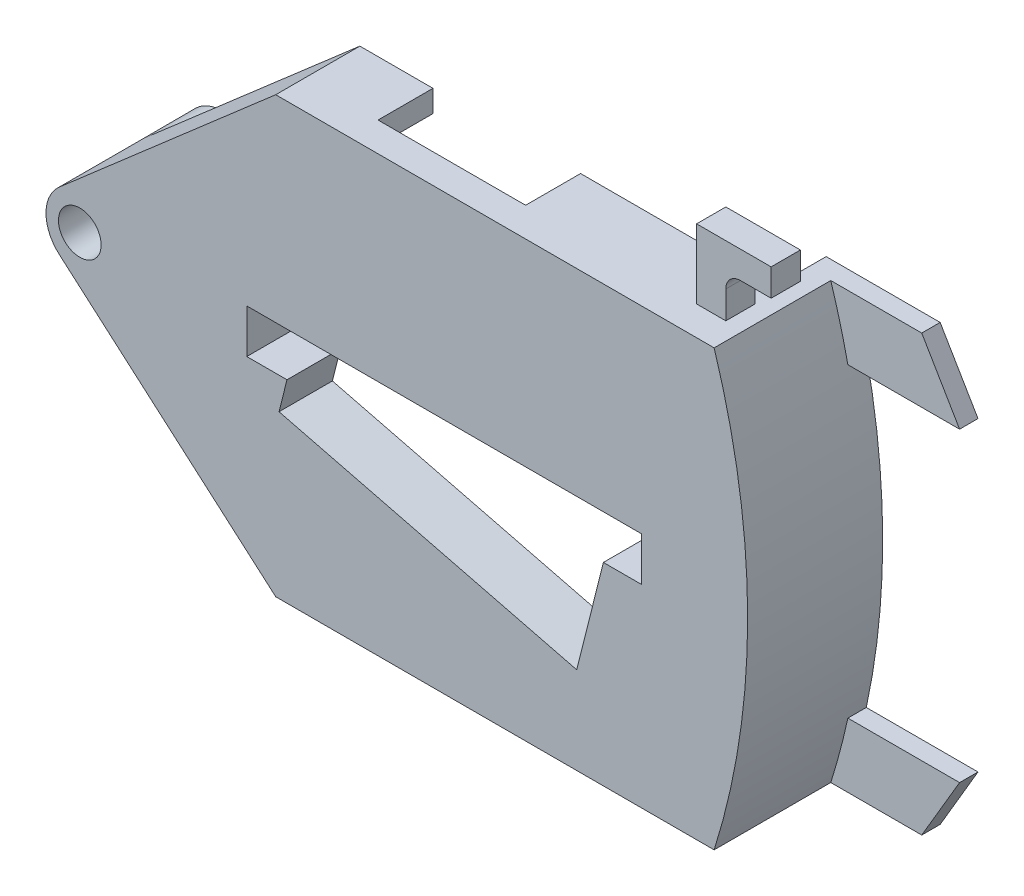
SolidWorks part; units mm, degrees
material "PW50:30:C1:0:1:2:Re:16:Tr:20:"
ref_plane "Plane1" through (0, 0, 0) normal (0, 0, 1) x (1, 0, 0)
ref_plane "Plane2" through (0, 0, 0) normal (0, 1, 0) x (1, 0, 0)
ref_plane "Plane3" through (0, 0, 0) normal (1, 0, 0) x (0, 0, -1)
other "Configuration Table"
sketch "Sketch1" plane through (0, 0, 0) normal (0, 0, 1) x (1, 0, 0)
  line L0 (-12.6668, 0) -> (55.8663, 0) construction
  line L1 (0, 0) -> (17.1073, 14.875)
  line L2 (0, 0) -> (17.1073, -14.875)
  line L3 (17.1073, 14.875) -> (47.1073, 14.875)
  line L4 (17.1073, -14.875) -> (47.1073, -14.875)
  arc A0 (47.1073, -14.875) -> (47.1073, 14.875) centre (0, 0) ccw
  dimension "D2" = 49.4
  dimension "D1" = 29.75
  dimension "D3" = 30
extrude "Base-Extrude" add sketch "Sketch1" along normal blind 5.76
sketch "Sketch2" plane through (0, 0, 5.76) normal (0, 0, 1) x (1, 0, 0)
  line L2 (0, 0) -> (17.1073, 14.875) construction
  line L3 (0, 0) -> (17.1073, -14.875) construction
  circle A0 centre (4.0387, 0) radius 2.65
  dimension "D1" = 5.3
extrude "Boss-Extrude1" add sketch "Sketch2" against normal blind 9.45
sketch "Sketch3" plane through (0, 0, 5.76) normal (0, 0, 1) x (1, 0, 0)
  line L0 (0, 0) -> (17.1073, -14.875) construction
  line L1 (0, 0) -> (17.1073, 14.875) construction
  line L2 (0, 0) -> (2.2999, -1.9998)
  line L3 (0, 0) -> (2.2999, 1.9998)
  arc A0 (2.2999, 1.9998) -> (2.2999, -1.9998) centre (4.0387, 0) ccw construction
  arc A1 (2.2999, 1.9998) -> (2.2999, -1.9998) centre (4.0387, 0) ccw
extrude "Cut-Extrude3" cut sketch "Sketch3" against normal through all
sketch "Sketch4" plane through (0, 0, -3.69) normal (0, 0, -1) x (-1, 0, 0)
  circle A0 centre (-4.0387, 0) radius 1.37
  dimension "D1" = 2.74
extrude "Boss-Extrude2" add sketch "Sketch4" along normal blind 2.64 draft 1 draft outward yes
sketch "Sketch6" plane through (0, 0, 5.76) normal (0, 0, 1) x (1, 0, 0)
  line L0 (1.3887, 0) -> (49.4, 0) construction
  line L1 (1.3887, 0) -> (1.3887, 1.0249) construction
  arc A1 (47.1073, -14.875) -> (47.1073, 14.875) centre (0, 0) ccw construction
  arc A2 (2.2999, 1.9998) -> (2.2999, -1.9998) centre (4.0387, 0) ccw construction
  dimension "D1" = 48.0113
sketch "Sketch7" plane through (0, 0, 5.76) normal (0, 0, 1) x (1, 0, 0)
  circle A2 centre (3.7016, 0) radius 1.15
  dimension "D1" = 2.3
extrude "Cut-Extrude4" cut sketch "Sketch7" against normal offset from surface (11.09 mm away) 1 up to face at (2.6226, 0, -6.33)
sketch "Sketch8" plane through (0, 0, 5.76) normal (0, 0, 1) x (1, 0, 0)
  line L0 (-0.719, 1.37) -> (50.999, 1.37) construction
  line L1 (15.1282, 1.37) -> (42.1282, 1.37)
  line L2 (42.1282, 1.37) -> (42.1282, -1.63)
  line L3 (42.1282, -1.63) -> (39.5282, -1.63)
  line L4 (39.5282, -1.63) -> (37.7042, -8.9048)
  line L5 (37.7042, -8.9048) -> (17.3347, -3.7977)
  line L6 (17.3347, -3.7977) -> (17.8782, -1.63)
  line L7 (17.8782, -1.63) -> (15.1282, -1.63)
  line L8 (15.1282, -1.63) -> (15.1282, 1.37)
  circle A0 centre (4.0387, 0) radius 1.37 construction
  dimension "D1" = 27
  dimension "D2" = 21
  dimension "D3" = 3
  dimension "D4" = 3
  dimension "D5" = 7.5
  dimension "D6" = 2.6
  dimension "D7" = 2.75
  dimension "D8" = 2.2348
extrude "Cut-Extrude5" cut sketch "Sketch8" against normal through all
sketch "Sketch9" plane through (0, 0, 0) normal (0, 0, -1) x (-1, 0, 0)
  line L12 (-3.2841, 0.8678) -> (-17.6682, 13.375)
  line L13 (-17.6682, 13.375) -> (-45.9948, 13.375)
  line L14 (-17.6682, -13.375) -> (-45.9948, -13.375)
  line L15 (-3.2841, -0.8678) -> (-17.6682, -13.375)
  line L16 (-5.0857, 2.4344) -> (-17.6682, 13.375)
  line L17 (-17.6682, 13.375) -> (-45.9948, 13.375)
  line L18 (-17.6682, -13.375) -> (-45.9948, -13.375)
  line L19 (-5.0857, -2.4344) -> (-17.6682, -13.375)
  circle A4 centre (-4.0387, 0) radius 2.65 construction
  arc A5 (-45.9948, 13.375) -> (-45.9948, -13.375) centre (0, 0) ccw
  arc A6 (-45.9948, 13.375) -> (-45.9948, -13.375) centre (0, 0) ccw
  arc A7 (-5.0857, 2.4344) -> (-5.0857, -2.4344) centre (-4.0387, 0) ccw
  dimension "D1" = 1.5
extrude "Cut-Extrude6" cut sketch "Sketch9" against normal offset from surface (3.76 mm away) 2 up to face at (4.8516, 0, 5.76)
sketch "Sketch10" plane through (0, 0, 3.76) normal (0, 0, -1) x (-1, 0, 0)
  line L0 (-15.1282, 1.37) -> (-15.1282, -1.63) construction
  line L1 (-15.1282, -1.63) -> (-17.8782, -1.63) construction
  line L2 (-17.8782, -1.63) -> (-17.3347, -3.7977) construction
  line L3 (-17.3347, -3.7977) -> (-37.7042, -8.9048) construction
  line L4 (-37.7042, -8.9048) -> (-39.5282, -1.63) construction
  line L5 (-39.5282, -1.63) -> (-42.1282, -1.63) construction
  line L6 (-42.1282, -1.63) -> (-42.1282, 1.37) construction
  line L7 (-42.1282, 1.37) -> (-15.1282, 1.37) construction
  line L8 (-43.1282, -2.63) -> (-43.1282, 2.37)
  line L9 (-40.3084, -2.63) -> (-43.1282, -2.63)
  line L10 (-38.431, -10.118) -> (-40.3084, -2.63)
  line L11 (-16.1215, -4.5245) -> (-38.431, -10.118)
  line L12 (-16.5965, -2.63) -> (-16.1215, -4.5245)
  line L13 (-14.1282, -2.63) -> (-16.5965, -2.63)
  line L14 (-14.1282, 2.37) -> (-14.1282, -2.63)
  line L15 (-43.1282, 2.37) -> (-14.1282, 2.37)
  line L16 (-43.1282, -2.63) -> (-43.1282, 2.37)
  line L17 (-40.3084, -2.63) -> (-43.1282, -2.63)
  line L18 (-38.431, -10.118) -> (-40.3084, -2.63)
  line L19 (-16.1215, -4.5245) -> (-38.431, -10.118)
  line L20 (-16.5965, -2.63) -> (-16.1215, -4.5245)
  line L21 (-14.1282, -2.63) -> (-16.5965, -2.63)
  line L22 (-14.1282, 2.37) -> (-14.1282, -2.63)
  line L23 (-43.1282, 2.37) -> (-14.1282, 2.37)
  line L24 (-15.1282, 1.37) -> (-15.1282, -1.63)
  line L25 (-15.1282, -1.63) -> (-17.8782, -1.63)
  line L26 (-17.8782, -1.63) -> (-17.3347, -3.7977)
  line L27 (-17.3347, -3.7977) -> (-37.7042, -8.9048)
  line L28 (-37.7042, -8.9048) -> (-39.5282, -1.63)
  line L29 (-39.5282, -1.63) -> (-42.1282, -1.63)
  line L30 (-42.1282, -1.63) -> (-42.1282, 1.37)
  line L31 (-42.1282, 1.37) -> (-15.1282, 1.37)
  dimension "D1" = 1
extrude "Boss-Extrude3" add sketch "Sketch10" along normal blind 1.65
sketch "Sketch11" plane through (0, 14.875, 0) normal (0, 1, 0) x (-1, 0, 0)
  line L0 (-32.2073, 0) -> (-22.1073, 0)
  line L1 (-32.2073, 0) -> (-32.2073, 3.76)
  line L2 (-22.1073, 3.76) -> (-32.2073, 3.76)
  line L3 (-22.1073, 3.76) -> (-22.1073, 0)
  line L4 (-17.1073, 0) -> (-47.1073, 0) construction
  line L5 (-17.1073, 5.76) -> (-17.1073, 0) construction
  line L6 (-17.6682, 3.76) -> (-45.9948, 3.76) construction
  dimension "D1" = 5
  dimension "D2" = 10.1
extrude "Cut-Extrude7" cut sketch "Sketch11" against normal up to surface (1.5 mm away) up to face at (31.8315, 13.375, 1.88)
sketch "Sketch12" plane through (0, -14.875, 0) normal (0, -1, 0) x (1, 0, 0)
  line L0 (22.1073, 0) -> (22.1073, 3.76) construction
  line L1 (32.2073, 3.76) -> (32.2073, 0) construction
  line L2 (22.1073, 0) -> (22.1073, 1.65)
  line L3 (32.2073, 1.65) -> (32.2073, 0)
  line L4 (32.2073, 1.65) -> (22.1073, 1.65)
  line L5 (32.2073, 0) -> (22.1073, 0)
  dimension "D1" = 1.65
extrude "Cut-Extrude8" cut sketch "Sketch12" against normal up to surface (1.5 mm away) up to face at (31.8315, -13.375, 1.88)
sketch "Sketch13" plane through (0, 0, 3.76) normal (0, 0, -1) x (-1, 0, 0)
  line L4 (-17.6682, -13.375) -> (-17.6682, -9.095) construction
  line L5 (-18.3782, -13.375) -> (-18.3782, -9.095)
  line L6 (-17.6682, -13.375) -> (-22.1073, -13.375) construction
  line L7 (-18.3782, -9.095) -> (-16.9582, -9.095)
  line L8 (-16.9582, -9.095) -> (-16.9582, -12.7576)
  line L9 (-5.0857, -2.4344) -> (-17.6682, -13.375) construction
  line L10 (-16.9582, -12.7576) -> (-17.6682, -13.375)
  line L11 (-17.6682, -13.375) -> (-18.3782, -13.375)
  dimension "D1" = 1.42
  dimension "D2" = 4.28
extrude "Boss-Extrude4" add sketch "Sketch13" along normal up to surface (3.76 mm away) up to face at (14.3855, -10.2226, 0)
fillet "Fillet1" radius 0.7 2 edges at (18.3782, -9.095, 1.88) (16.9582, -9.095, 1.88)
sketch "Sketch14" plane through (0, 0, 0) normal (0, 0, -1) x (-1, 0, 0)
  line L1 (-38.431, -10.118) -> (-38.431, -18.0474) construction
  line L2 (-38.431, -10.675) -> (-39.801, -10.675)
  line L3 (-39.801, -10.675) -> (-39.801, -13.375)
  line L4 (-32.2073, -13.375) -> (-45.9948, -13.375) construction
  line L5 (-39.801, -13.375) -> (-45.9948, -13.375)
  line L6 (-45.9948, -13.375) -> (-47.1073, -14.875)
  line L7 (-47.1073, -14.875) -> (-38.431, -14.875)
  line L8 (-38.431, -14.875) -> (-38.431, -10.675)
  dimension "D1" = 4.2
  dimension "D2" = 1.37
extrude "Boss-Extrude5" add sketch "Sketch14" along normal blind 1.42 and the other way up to surface (3.76 mm away) other way up to face at (28.2463, -2.5528, 3.76)
fillet "Fillet5" radius 0.685 2 edges at (38.431, -10.675, 1.17) (39.801, -10.675, 1.17)
sketch "Sketch15" plane through (0, 0, 0) normal (0, 0, -1) x (-1, 0, 0)
  line L2 (-47.1073, 14.875) -> (-45.5318, 14.875)
  line L4 (-47.1073, -14.875) -> (-45.5318, -14.875)
  arc A0 (-45.9948, 13.375) -> (-45.9948, -13.375) centre (0, 0) ccw construction
  arc A1 (-47.1073, 14.875) -> (-47.1073, -14.875) centre (0, 0) ccw construction
  arc A2 (-45.5318, 14.875) -> (-45.5318, -14.875) centre (0, 0) ccw
  arc A3 (-47.1073, 14.875) -> (-47.1073, -14.875) centre (0, 0) ccw
extrude "Boss-Extrude6" add sketch "Sketch15" along normal blind 3.48
sketch "Sketch16" plane through (0, 0, -3.48) normal (0, 0, -1) x (-1, 0, 0)
  line L0 (-47.1073, -14.875) -> (-45.5318, -14.875) construction
  line L1 (-47.1073, 14.875) -> (-45.5318, 14.875) construction
  line L2 (-47.1073, -14.875) -> (-45.5318, -14.875)
  line L3 (-47.1073, 14.875) -> (-45.5318, 14.875)
  line L4 (0, 0) -> (-58.7476, 0) construction
  line L5 (-47.1073, 14.875) -> (-53.3318, 14.875)
  line L6 (-47.1073, -14.875) -> (-53.3318, -14.875)
  line L7 (-53.3318, 14.875) -> (-55.9216, 10.4705)
  line L8 (-53.3318, -14.875) -> (-55.9216, -10.4705)
  line L9 (-55.9216, 10.4705) -> (-46.7416, 10.4705)
  line L10 (-55.9216, -10.4705) -> (-46.7416, -10.4705)
  arc A0 (-45.5318, 14.875) -> (-45.5318, -14.875) centre (0, 0) ccw construction
  arc A1 (-45.5318, 14.875) -> (-46.7416, 10.4705) centre (0, 0) ccw
  arc A3 (-46.7416, -10.4705) -> (-45.5318, -14.875) centre (0, 0) ccw
  dimension "D1" = 7.8
  dimension "D2" = 9.18
extrude "Boss-Extrude7" add sketch "Sketch16" against normal blind 1.26
sketch "Sketch17" plane through (0, 0, 5.76) normal (0, 0, 1) x (1, 0, 0)
  line L0 (45.9073, 14.875) -> (45.9073, 17.765)
  line L1 (17.1073, 14.875) -> (47.1073, 14.875) construction
  line L2 (45.9073, 17.765) -> (49.0073, 17.765)
  line L3 (49.0073, 17.765) -> (49.0073, 19.625)
  line L4 (49.0073, 19.625) -> (43.9073, 19.625)
  line L5 (43.9073, 19.625) -> (43.9073, 14.875)
  line L6 (43.9073, 14.875) -> (45.9073, 14.875)
  dimension "D1" = 5.1
  dimension "D2" = 1.86
  dimension "D3" = 4.75
  dimension "D4" = 2
  dimension "D5" = 1.2
extrude "Boss-Extrude8" add sketch "Sketch17" against normal blind 4
sketch "Sketch18" plane through (43.9073, 0, 0) normal (-1, 0, 0) x (0, 0, 1)
  line L0 (3.76, 19.625) -> (3.76, 13.375) construction
  line L1 (3.76, 19.625) -> (3.76, 14.875)
  line L4 (5.76, 14.875) -> (5.76, 19.625)
  line L5 (5.76, 19.625) -> (1.76, 19.625)
  line L6 (1.76, 19.625) -> (1.76, 14.875)
  line L7 (1.76, 14.875) -> (5.76, 14.875)
  line L8 (5.76, 14.875) -> (5.76, 19.625)
  line L9 (5.76, 19.625) -> (3.76, 19.625)
  line L11 (3.76, 14.875) -> (5.76, 14.875)
  dimension "D1" = 0
extrude "Cut-Extrude9" cut sketch "Sketch18" against normal through all
fillet "Fillet2" radius 1 1 edges at (45.9073, 17.765, 2.76)
sketch "Sketch21" plane through (0, 0, 1.18) normal (0, 0, -1) x (-1, 0, 0)
  circle A0 centre (-3.7016, 0) radius 1.46 construction
  circle A1 centre (-3.7016, 0) radius 1.46
extrude "Cut-Extrude13" cut sketch "Sketch21" against normal up to surface (4.58 mm away) up to face at (22.4017, 0, 5.76)
